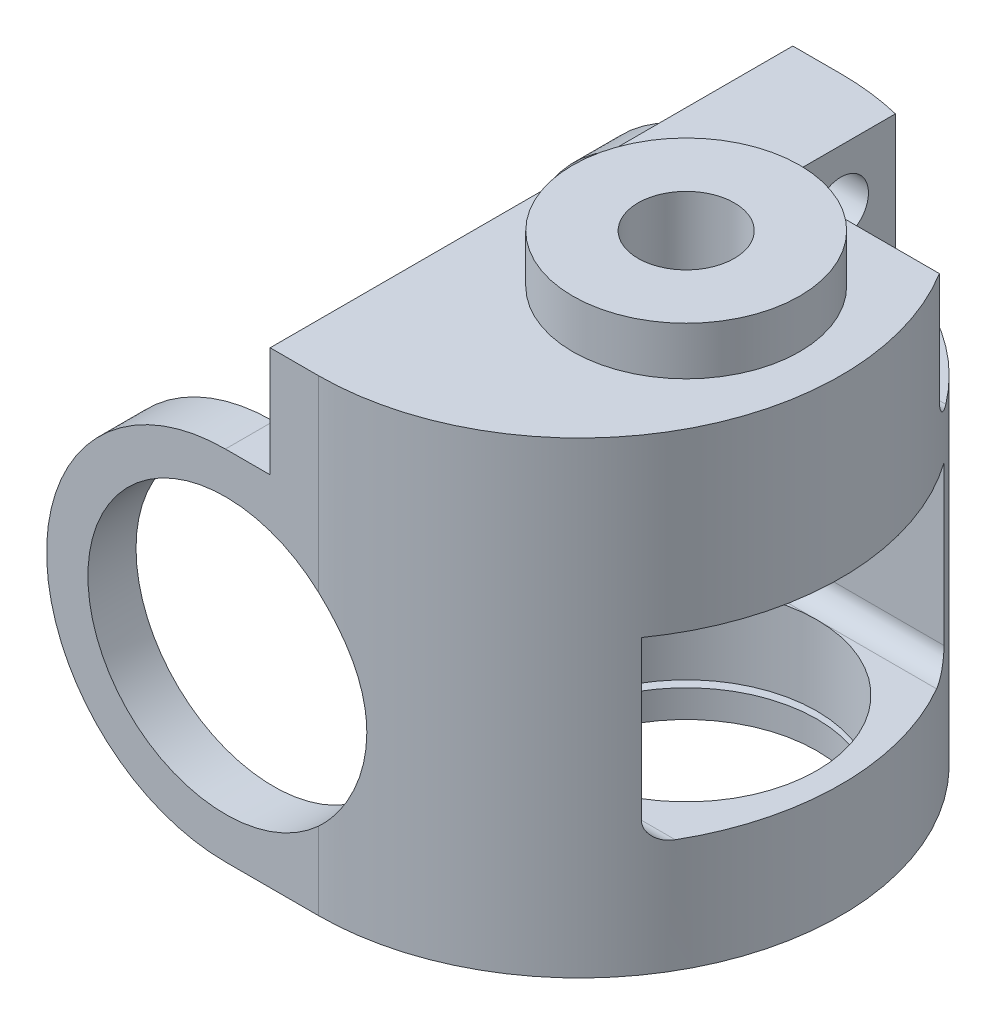
SolidWorks part; units mm, degrees
ref_plane "Plan de face" through (0, 0, 0) normal (0, 0, 1) x (1, 0, 0)
ref_plane "Plan de dessus" through (0, 0, 0) normal (0, 1, 0) x (1, 0, 0)
ref_plane "Plan de droite" through (0, 0, 0) normal (1, 0, 0) x (0, 0, -1)
sketch "Sketch2" plane through (0, 0, 0) normal (0, 1, 0) x (1, 0, 0)
  line L0 (-3.5, -19) -> (-3.5, 19)
  line L1 (-3.5, 19) -> (0, 19)
  line L2 (-3.5, -19) -> (0, -19)
  line L3 (19, 0) -> (19, 16.5672) construction
  arc A0 (0, -19) -> (0, 19) centre (0, 0) ccw
  circle A1 centre (7.75, 0) radius 3.5
  point P7 (-3.5, 0)
  dimension "D1" = 19
  dimension "D3" = 22.5
  dimension "D4" = 11.25
  dimension "D5" = 7
  dimension "D2" = 38
extrude "Boss-Extrude1" add sketch "Sketch2" along normal blind 34
sketch "Sketch19" plane through (0, 34, 0) normal (0, 1, 0) x (1, 0, 0)
  circle A0 centre (7.75, 0) radius 8.25
  circle A1 centre (7.75, 0) radius 3.5
  dimension "D1" = 16.5
  dimension "D2" = 7
extrude "Boss-Extrude3" add sketch "Sketch19" along normal blind 3.5
sketch "Sketch3" plane through (0, 0, 19) normal (0, 0, 1) x (1, 0, 0)
  line L3 (-3.5, 0) -> (-6.75, 0)
  line L4 (-6.75, 26) -> (-3.5, 26)
  line L5 (-3.5, 34) -> (-3.5, 0) construction
  arc A0 (-6.75, 26) -> (-6.75, 0) centre (-6.75, 13) ccw
  line M4 (-3.5, 34) -> (-3.5, 0)
  dimension "D1" = 26
  dimension "D2" = 3.25
extrude "Boss-Extrude2" add sketch "Sketch3" against normal blind 3.5 contours A0 M4 region at (-10.5428, 13, 19)
sketch "Sketch4" plane through (0, 0, 19) normal (0, 0, 1) x (1, 0, 0)
  circle A0 centre (-6.75, 13) radius 10
  dimension "D1" = 20
extrude "Cut-Extrude1" cut sketch "Sketch4" against normal up to surface (3.5 mm away) up to face at (-8.375, 13, 15.5)
pattern_linear "LPattern4" count 2 spacing 34.5 along (0, 0, -1) of "Boss-Extrude2", "Cut-Extrude1"
sketch "Sketch6" plane through (-3.5, 0, 0) normal (1, 0, 0) x (0, 0, -1)
  line L0 (15.5, 0) -> (-15.5, 0) construction
  line L1 (11, 21.25) -> (-11, 21.25)
  line L2 (11, 21.25) -> (11, 9.75)
  line L3 (9.5, 8.25) -> (-9.5, 8.25)
  line L4 (-11, 21.25) -> (-11, 9.75)
  arc A0 (-11, 9.75) -> (-9.5, 8.25) centre (-9.5, 9.75) ccw
  arc A1 (11, 9.75) -> (9.5, 8.25) centre (9.5, 9.75) cw
  point P6 (0, 8.25)
  point P10 (-11, 8.25)
  point P13 (11, 8.25)
  dimension "D4" = 1.5
  dimension "D1" = 8.25
  dimension "D2" = 22
  dimension "D3" = 13
extrude "Cut-Extrude3" cut sketch "Sketch6" along normal through all
sketch "Sketch7" plane through (0, 0, 15.5) normal (0, 0, -1) x (-1, 0, 0)
  circle A3 centre (6.75, 13) radius 13.5
  dimension "D3" = 27
extrude "Cut-Extrude4" cut sketch "Sketch7" along normal blind 4.5 contours A3
pattern_linear "LPattern3" count 2 spacing 26.5 along (0, 0, -1) of "Cut-Extrude4"
sketch "Sketch16" plane through (-3.5, 0, 0) normal (-1, 0, 0) x (0, 0, 1)
  line L0 (19, 34) -> (19, 26) construction
  line L1 (-19, 34) -> (19, 34) construction
  point P0 (11, 31.5)
  dimension "D1" = 8
  dimension "D2" = 2.5
hole_wizard "M2 Tapped Hole1" positions "Sketch16" profile "Sketch15" tap size "M2" standard "ISO"
sketch "Sketch15" plane through (-3.5, 31.5, 11) normal (0, 1, 0) x (0, 0, 1)
  line L0 (0, 0) -> (0, 5.9807)
  line L1 (0, 5.9807) -> (0.8, 5.5)
  line L2 (0.8, 5.5) -> (0.8, 0)
  line L5 (0.8, 0) -> (0, 0)
  line L10 (0, 5.9807) -> (-0.8, 5.5) construction
  line L11 (0, -6.35) -> (0, 107.95) construction
  dimension "Tap Drill Dia." = 1.6
  dimension "Tap Drill Depth" = 5.5
  dimension "Drill Angle" = 118
cosmetic thread "Hole Thread1" parameters "D1"=4.5, "D2"=2
sketch "Sketch17" plane through (-3.5, 0, 0) normal (-1, 0, 0) x (0, 0, 1)
  line L0 (-19, 34) -> (-19, 26) construction
  line L1 (-19, 34) -> (19, 34) construction
  circle A1 centre (-14.5, 30) radius 2
  dimension "D1" = 4
  dimension "D2" = 4.5
  dimension "D3" = 4
extrude "Cut-Extrude5" cut sketch "Sketch17" against normal blind 8
sketch "Sketch18" plane through (4.5, 0, 0) normal (-1, 0, 0) x (0, 0, 1)
  line L0 (-19, 34) -> (-19, 26) construction
  line L1 (-19, 24.5) -> (-11.5, 24.5)
  line L2 (-19, 24.5) -> (-19, 34)
  line L3 (-19, 34) -> (-10, 34)
  line L4 (-10, 26) -> (-10, 34)
  line L5 (-19, 34) -> (19, 34) construction
  arc A2 (-10, 26) -> (-11.5, 24.5) centre (-11.5, 26) cw
  dimension "D1" = 9.5
  dimension "D2" = 9
  dimension "D3" = 1.5
extrude "Cut-Extrude6" cut sketch "Sketch18" against normal up to next
sketch "Sketch20" plane through (0, 21.25, 0) normal (0, -1, 0) x (1, 0, 0)
  circle A0 centre (7.75, 0) radius 9.75
  dimension "D1" = 19.5
extrude "Cut-Extrude7" cut sketch "Sketch20" against normal blind 6.25
sketch "Sketch21" plane through (0, 27.5, 0) normal (0, -1, 0) x (1, 0, 0)
  circle A0 centre (7.75, 0) radius 8.5
  dimension "D1" = 17
extrude "Cut-Extrude8" cut sketch "Sketch21" against normal blind 0.5
sketch "Sketch22" plane through (0, 8.25, 0) normal (0, 1, 0) x (1, 0, 0)
  circle A0 centre (7.75, 0) radius 9.5
  dimension "D1" = 19
extrude "Cut-Extrude9" cut sketch "Sketch22" against normal blind 5.75
sketch "Sketch23" plane through (0, 2.5, 0) normal (0, 1, 0) x (1, 0, 0)
  circle A0 centre (7.75, 0) radius 10.5
  dimension "D1" = 21
extrude "Cut-Extrude10" cut sketch "Sketch23" against normal blind 0.5
sketch "Sketch24" plane through (0, 2, 0) normal (0, 1, 0) x (1, 0, 0)
  circle A0 centre (7.75, 0) radius 9.5
  dimension "D1" = 19
extrude "Cut-Extrude11" cut sketch "Sketch24" against normal blind 2
